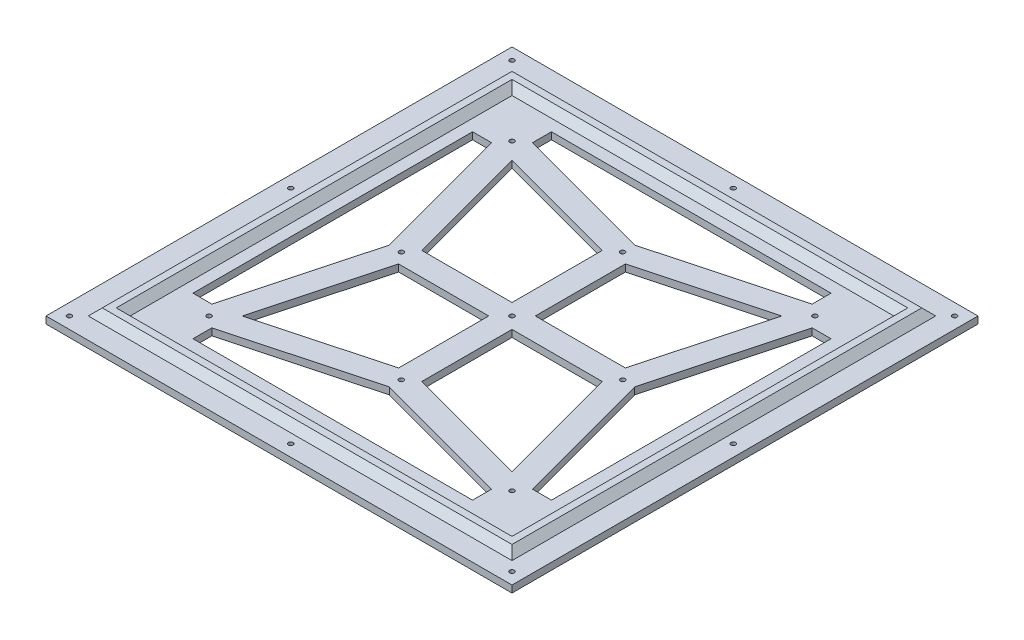
SolidWorks part; units mm, degrees
ref_plane "Front Plane" through (0, 0, 0) normal (0, 0, 1) x (1, 0, 0)
ref_plane "Top Plane" through (0, 0, 0) normal (0, 1, 0) x (1, 0, 0)
ref_plane "Right Plane" through (0, 0, 0) normal (1, 0, 0) x (0, 0, -1)
sketch "Sketch1" plane through (0, 0, 0) normal (0, 1, 0) x (1, 0, 0)
  line L1 (-100, 100) -> (100, 100)
  line L2 (-100, 100) -> (-100, -100)
  line L3 (-100, -100) -> (100, -100)
  line L4 (100, 100) -> (100, -100)
  line L5 (-100, 100) -> (100, -100) construction
  line L6 (-100, -100) -> (100, 100) construction
  point P0 (0, 0)
  dimension "D1" = 200
extrude "Boss-Extrude1" add sketch "Sketch1" along normal blind 3
sketch "Sketch2" plane through (0, 3, 0) normal (0, 1, 0) x (1, 0, 0)
  line L0 (0, 0) -> (0, -95) construction
  line L1 (-100, -100) -> (100, -100) construction
  line L2 (-100, -100) -> (-100, 100) construction
  line L3 (-100, 100) -> (100, 100) construction
  line L4 (100, -100) -> (100, 100) construction
  line L5 (-100, -100) -> (100, 100) construction
  line L6 (-100, 100) -> (100, -100) construction
  line L7 (95, -95) -> (-95, -95) construction
  line L8 (95, -95) -> (95, 95) construction
  line L9 (95, 95) -> (-95, 95) construction
  line L10 (-95, 95) -> (-95, -95) construction
  line L11 (0, 0) -> (0, 95) construction
  line L12 (0, 0) -> (-95, 95) construction
  line L13 (0, 0) -> (95, 95) construction
  line L14 (0, 0) -> (-95, -95) construction
  line L15 (0, 0) -> (95, -95) construction
  line L16 (0, 0) -> (95, 0) construction
  line L17 (0, 0) -> (-95, 0) construction
  circle A1 centre (95, -95) radius 1
  circle A2 centre (0, -95) radius 1
  circle A3 centre (-95, -95) radius 1
  circle A4 centre (-95, 0) radius 1
  circle A5 centre (-95, 95) radius 1
  circle A6 centre (0, 0) radius 1
  circle A7 centre (95, 0) radius 1
  circle A8 centre (95, 95) radius 1
  circle A9 centre (0, 95) radius 1
  circle A10 centre (-47.5, 0) radius 1
  circle A11 centre (47.5, 0) radius 1
  circle A12 centre (0, 47.5) radius 1
  circle A13 centre (0, -47.5) radius 1
  circle A14 centre (0, 0) radius 91.9239 construction
  circle A15 centre (-65, 65) radius 1
  circle A16 centre (-65, -65) radius 1
  circle A17 centre (65, -65) radius 1
  circle A18 centre (65, 65) radius 1
  point P0 (0, 0)
  point P42 (0, 0)
  point P43 (0, 0)
  point P44 (0, 0)
  dimension "D1" = 2
  dimension "D2" = 5
  dimension "D3" = 30
  dimension "D4" = 95
  dimension "D5" = 190
  dimension "D6" = 30
  dimension "D7" = 160
  dimension "D8" = 47.5
  dimension "D9" = 142.5
extrude "Cut-Extrude1" cut sketch "Sketch2" against normal up to next
sketch "Sketch4" plane through (0, 3, 0) normal (0, 1, 0) x (1, 0, 0)
  line L1 (-87.9289, 87.9289) -> (87.9289, 87.9289)
  line L2 (-87.9289, 87.9289) -> (-87.9289, -87.9289)
  line L3 (-87.9289, -87.9289) -> (87.9289, -87.9289)
  line L4 (87.9289, 87.9289) -> (87.9289, -87.9289)
  line L5 (-87.9289, 87.9289) -> (87.9289, -87.9289) construction
  line L6 (-87.9289, -87.9289) -> (87.9289, 87.9289) construction
  line L7 (-84.9289, 84.9289) -> (84.9289, 84.9289)
  line L8 (-84.9289, 84.9289) -> (-84.9289, -84.9289)
  line L9 (-84.9289, -84.9289) -> (84.9289, -84.9289)
  line L10 (84.9289, 84.9289) -> (84.9289, -84.9289)
  line L11 (-84.9289, 84.9289) -> (84.9289, -84.9289) construction
  line L12 (-84.9289, -84.9289) -> (84.9289, 84.9289) construction
  circle A0 centre (95, -95) radius 1 construction
  point P0 (0, 0)
  point P6 (0, 0)
  dimension "D1" = 3
  dimension "D2" = 10
extrude "Boss-Extrude2" add sketch "Sketch4" along normal blind 3
chamfer "Chamfer1" distance 3 angle 45 8 edges at (0, 3, -87.9289) (-87.9289, 3, 0) (0, 3, 87.9289) (87.9289, 3, 0) (0, 3, 84.9289) (84.9289, 3, 0) (0, 3, -84.9289) (-84.9289, 3, 0)
sketch "Sketch5" plane through (0, 3, 0) normal (0, 1, 0) x (1, 0, 0)
  line L1 (65, 65) -> (0, 47.5) construction
  line L2 (0, 47.5) -> (-65, 65) construction
  line L6 (65, 65) -> (65, 81.9289) construction
  line L7 (81.9289, 81.9289) -> (-81.9289, 81.9289) construction
  line L8 (65, 81.9289) -> (-65, 81.9289) construction
  line L9 (-65, 81.9289) -> (-65, 65) construction
  line L10 (0, 52.678) -> (-60, 68.8319)
  line L11 (-60, 76.9289) -> (-60, 68.8319)
  line L12 (60, 76.9289) -> (-60, 76.9289)
  line L13 (60, 68.8319) -> (60, 76.9289)
  line L14 (60, 68.8319) -> (0, 52.678)
  line L15 (52.678, 0) -> (68.8319, 60)
  line L16 (76.9289, 60) -> (68.8319, 60)
  line L17 (76.9289, -60) -> (76.9289, 60)
  line L18 (68.8319, -60) -> (76.9289, -60)
  line L19 (68.8319, -60) -> (52.678, 0)
  line L20 (0, -52.678) -> (60, -68.8319)
  line L21 (60, -76.9289) -> (60, -68.8319)
  line L22 (-60, -76.9289) -> (60, -76.9289)
  line L23 (-60, -68.8319) -> (-60, -76.9289)
  line L24 (-60, -68.8319) -> (0, -52.678)
  line L25 (-52.678, 0) -> (-68.8319, -60)
  line L26 (-76.9289, -60) -> (-68.8319, -60)
  line L27 (-76.9289, 60) -> (-76.9289, -60)
  line L28 (-68.8319, 60) -> (-76.9289, 60)
  line L29 (-68.8319, 60) -> (-52.678, 0)
  line L30 (-65, 65) -> (-47.5, 0) construction
  line L31 (-47.5, 0) -> (0, 0) construction
  line L32 (0, 0) -> (0, 47.5) construction
  line L33 (-5, 5) -> (-5, 43.6681)
  line L34 (-5, 43.6681) -> (-57.9143, 57.9143)
  line L35 (-57.9143, 57.9143) -> (-43.6681, 5)
  line L36 (-43.6681, 5) -> (-5, 5)
  line L37 (5, 5) -> (43.6681, 5)
  line L38 (43.6681, 5) -> (57.9143, 57.9143)
  line L39 (57.9143, 57.9143) -> (5, 43.6681)
  line L40 (5, 43.6681) -> (5, 5)
  line L41 (5, -5) -> (5, -43.6681)
  line L42 (5, -43.6681) -> (57.9143, -57.9143)
  line L43 (57.9143, -57.9143) -> (43.6681, -5)
  line L44 (43.6681, -5) -> (5, -5)
  line L45 (-5, -5) -> (-43.6681, -5)
  line L46 (-43.6681, -5) -> (-57.9143, -57.9143)
  line L47 (-57.9143, -57.9143) -> (-5, -43.6681)
  line L48 (-5, -43.6681) -> (-5, -5)
  line L49 (-5, 5) -> (5, -5) construction
  circle A3 centre (0, 0) radius 52.678 construction
  point P16 (0, 0)
  point P37 (0, 0)
  point P41 (0, 0)
  point P42 (0, 0)
  point P56 (0, 0)
  dimension "D5" = 10
  dimension "D1" = 5
  dimension "D3" = 5
  dimension "D2" = 4
  dimension "D4" = 4
extrude "Cut-Extrude2" cut sketch "Sketch5" against normal up to next
